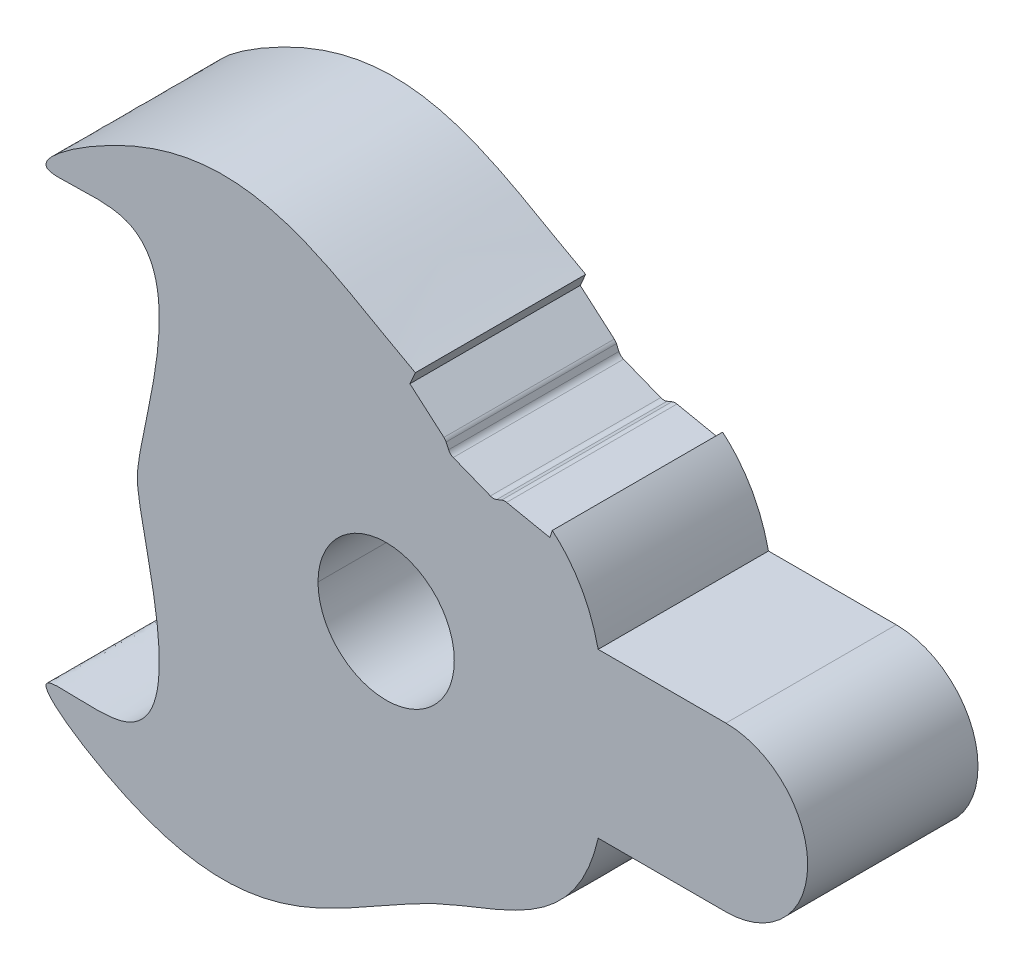
SolidWorks part; units mm, degrees
ref_plane "Front Plane" through (0, 0, 0) normal (0, 0, 1) x (1, 0, 0)
ref_plane "Top Plane" through (0, 0, 0) normal (0, 1, 0) x (1, 0, 0)
ref_plane "Right Plane" through (0, 0, 0) normal (1, 0, 0) x (0, 0, -1)
sketch "Sketch1" plane through (0, 0, 0) normal (0, 0, 1) x (1, 0, 0)
  line L2 (42.41, 9.6) -> (57.41, 9.6)
  line L6 (9.51, 0) -> (-11.6928, 0)
  line L7 (67.01, 0) -> (25.51, 0)
  arc A1 (67.01, 0) -> (57.41, 9.6) centre (57.41, 0) ccw
  arc A2 (9.51, 0) -> (25.51, 0) centre (17.51, 0.02) cw
  spline S0 degree 3 poles (-11.6928, 0) (-11.8393, 4.8945) (-2.3556, 29.35) (-27.8845, 24.1434) (0.6228, 43.5441) (18.6604, 24.2001) (39.8587, 20.776) (42.41, 9.6) knots 0 0 0 0 0.241029 0.319956 0.433187 0.773179 1 1 1 1
  point P9 (0, 0)
  point P11 (0, 0)
  point P13 (0, 0)
  point P14 (0, 0)
  point P16 (42.41, 9.6)
  dimension "D2" = 8
  dimension "D3" = 9.51
  dimension "D5" = 25.6795
  dimension "D6" = 26.1273
  dimension "D12" = 9.9764
  dimension "D20" = 23.1433
  dimension "D9" = 16.9
  dimension "D10" = 9.6
  dimension "D22" = 17.51
  dimension "D4" = 9.8579
  dimension "D7" = 33.441
  dimension "D8" = 41.5
  dimension "D11" = 22.2157
  dimension "D13" = 11.6928
  dimension "D14" = 25.55
  dimension "D15" = 23.93
  dimension "D16" = 9.6
  dimension "D17" = 2.25
  dimension "D18" = 1.63
  dimension "D19" = 21.7999
extrude "Boss-Extrude1" add sketch "Sketch1" along normal mid plane 20
mirror "Mirror1" about plane through (67.01, 0, 10) normal (0, 1, 0) of "Boss-Extrude1"
sketch "Sketch2" plane through (0, 0, 10) normal (0, 0, 1) x (1, 0, 0)
  line L12 (37.6, 20.83) -> (36.7457, 18.13)
  line L13 (36.7457, 18.13) -> (31.3572, 19.232)
  line L15 (30.1274, 18.724) -> (25.0122, 20.745)
  line L16 (25.0122, 20.745) -> (24.4616, 21.9563)
  line L17 (24.4616, 21.9563) -> (20.3012, 25.5536)
  line L18 (20.3012, 25.5536) -> (20.94, 26.9987)
  line L19 (37.6, 20.83) -> (20.94, 26.9987)
  line L20 (31.3572, 19.232) -> (30.1274, 18.724)
  spline S2 degree 3 poles (42.41, 9.6) (39.8587, 20.776) (18.6604, 24.2001) (0.6228, 43.5441) (-27.8845, 24.1434) (-2.3556, 29.35) (-11.8393, 4.8945) (-11.6928, 0) knots 0 0 0 0 0.226821 0.566813 0.680044 0.758971 1 1 1 1 construction
  dimension "D1" = 107
  dimension "D2" = 84
  dimension "D3" = 5.5
  dimension "D4" = 136
  dimension "D5" = 136
  dimension "D6" = 1.58
  dimension "D7" = 2.7
  dimension "D8" = 18.13
  dimension "D9" = 16.66
  dimension "D10" = 204.71
  dimension "D11" = 214
  dimension "D12" = 36.7457
extrude "Cut-Extrude1" cut sketch "Sketch2" against normal through all
fillet "Fillet1" radius 1 4 edges at (31.3572, 19.232, 0) (30.1274, 18.724, 0) (25.0122, 20.745, 0) (24.4616, 21.9563, 0)
